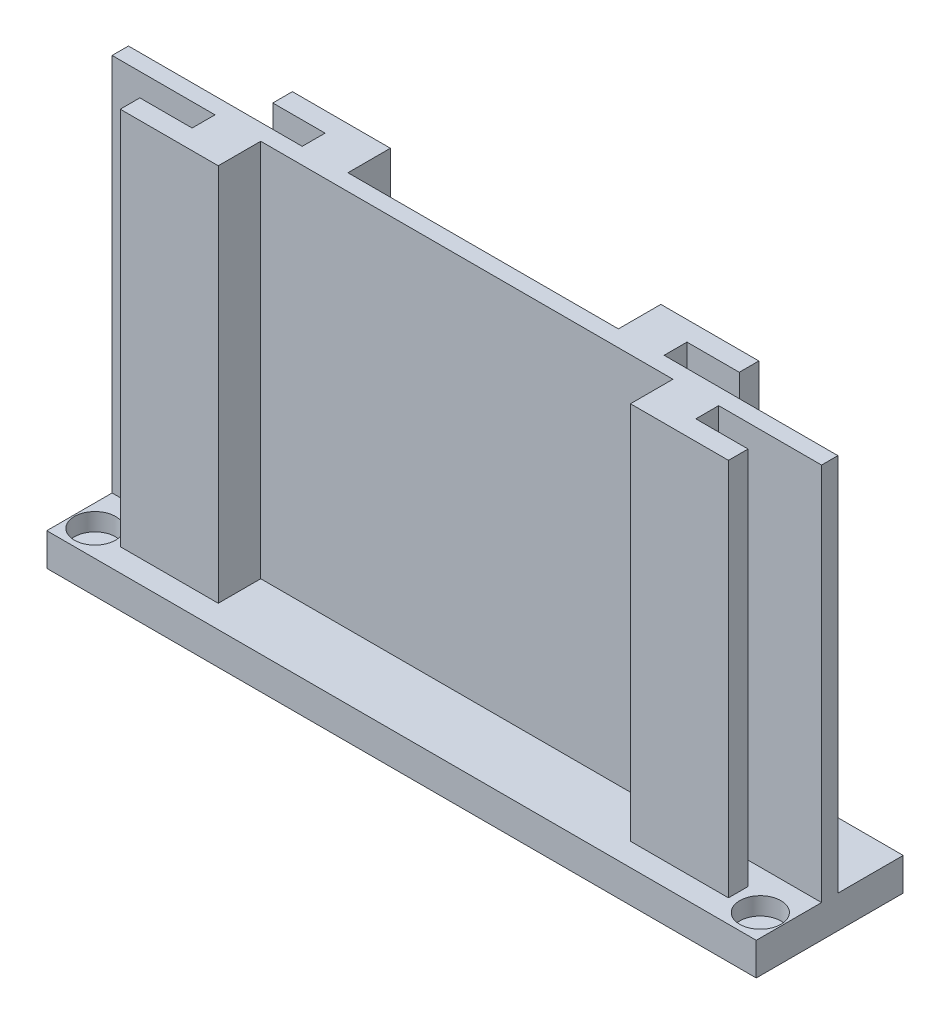
SolidWorks part; units mm, degrees
ref_plane "Front Plane" through (0, 0, 0) normal (0, 0, 1) x (1, 0, 0)
ref_plane "Top Plane" through (0, 0, 0) normal (0, 1, 0) x (1, 0, 0)
ref_plane "Right Plane" through (0, 0, 0) normal (1, 0, 0) x (0, 0, -1)
sketch "Sketch1" plane through (0, 0, 0) normal (0, 1, 0) x (1, 0, 0)
  line L1 (-54.3, -11.25) -> (54.3, -11.25)
  line L2 (-54.3, -11.25) -> (-54.3, 11.25)
  line L3 (-54.3, 11.25) -> (54.3, 11.25)
  line L4 (54.3, -11.25) -> (54.3, 11.25)
  line L5 (-54.3, -11.25) -> (54.3, 11.25) construction
  line L6 (-54.3, 11.25) -> (54.3, -11.25) construction
  point P0 (0, 0)
  dimension "D1" = 108.6
  dimension "D2" = 22.5
extrude "Boss-Extrude1" add sketch "Sketch1" along normal blind 5
sketch "Sketch2" plane through (0, 5, 0) normal (0, 1, 0) x (1, 0, 0)
  line L0 (-54.3, -11.25) -> (54.3, -11.25) construction
  line L2 (54.3, 11.25) -> (-54.3, 11.25) construction
  line L3 (0, 11.25) -> (0, -11.25) construction
  circle A4 centre (50.925, -7.25) radius 3.15 construction
  circle A5 centre (40.075, 7.25) radius 3.15 construction
  circle A6 centre (-50.925, -7.25) radius 3.15 construction
  circle A7 centre (-40.075, 7.25) radius 3.15 construction
  circle A8 centre (50.925, -7.25) radius 3.15
  circle A9 centre (40.075, 7.25) radius 3.15
  circle A10 centre (-50.925, -7.25) radius 3.15
  circle A11 centre (-40.075, 7.25) radius 3.15
extrude "Cut-Extrude1" cut sketch "Sketch2" against normal blind 2.7
sketch "Sketch3" plane through (0, 5, 0) normal (0, 1, 0) x (1, 0, 0)
  line L0 (-54.3, 0) -> (54.3, 0) construction
  line L1 (-54.3, 11.25) -> (-54.3, -11.25) construction
  line L2 (54.3, -11.25) -> (54.3, 11.25) construction
  line L3 (-38.55, -1.25) -> (-38.55, -4.75)
  line L4 (-54.3, 1.25) -> (54.3, 1.25)
  line L5 (-54.3, 1.25) -> (-54.3, -1.25)
  line L6 (-54.3, -1.25) -> (54.3, -1.25)
  line L7 (54.3, 1.25) -> (54.3, -1.25)
  line L8 (-38.55, -4.75) -> (-46.55, -4.75)
  line L9 (-46.55, -4.75) -> (-46.55, -7.75)
  line L14 (-46.55, -7.75) -> (-31.55, -7.75)
  line L15 (-31.55, -7.75) -> (-31.55, -1.25)
  line L16 (-38.55, -1.25) -> (-31.55, -1.25)
  line L17 (-27.7, 1.25) -> (-27.7, 4.75)
  line L18 (-27.7, 4.75) -> (-35.7, 4.75)
  line L19 (-35.7, 4.75) -> (-35.7, 7.75)
  line L24 (-35.7, 7.75) -> (-20.7, 7.75)
  line L25 (-20.7, 7.75) -> (-20.7, 1.25)
  line L26 (-27.7, 1.25) -> (-20.7, 1.25)
  point P10 (-54.3, 0)
  point P13 (0, 0)
  point P16 (0, 0)
  point P18 (-46.3288, -9.75)
  point P19 (-35.2937, 9.75)
  line M20 (54.3, -11.25) -> (54.3, 11.25)
  line M22 (-54.3, 11.25) -> (-54.3, -11.25)
  dimension "D1" = 2.5
  dimension "D2" = 3
  dimension "D3" = 8
  dimension "D4" = 7.75
  dimension "D5" = 3.5
  dimension "D7" = 22.75
  dimension "D10" = 3.5
  dimension "D11" = 3
  dimension "D12" = 18.6
  dimension "D13" = 33.6
  dimension "D16" = 8
extrude "Boss-Extrude2" add sketch "Sketch3" along normal blind 58 contours L0 L7 L4 M22 | L0 L5 L6 M20 | L14 L15 L6 L3 L8 L9 | L25 L24 L19 L18 L17 L4 region at (0, 5, -0.625) region at (0, 5, 0.625) region at (-26.7899, 5, -5.1043) region at (-37.6399, 5, 5.1043)
ref_plane "Plane1" through (0, 0, 0) normal (1, 0, 0) x (0, 0, -1)
mirror "Mirror1" about plane through (0, 0, 0) normal (1, 0, 0) of "Boss-Extrude2"
